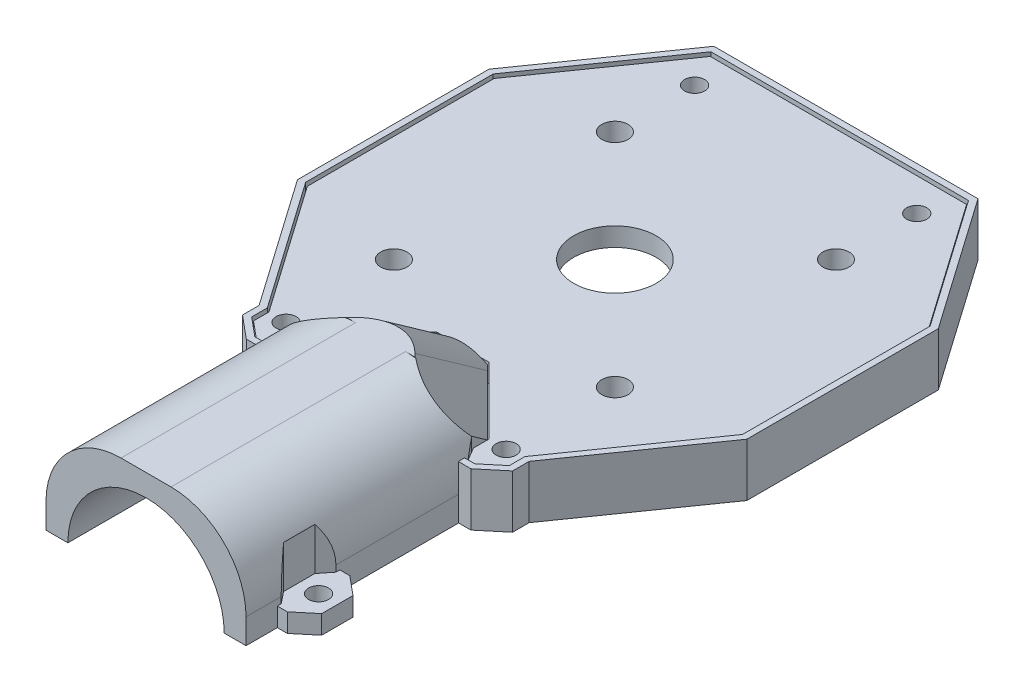
SolidWorks part; units mm, degrees
other "Base"
other "Plate"
material "ABS"
ref_plane "Front Plane" through (0, 0, 0) normal (0, 0, 1) x (1, 0, 0)
ref_plane "Top Plane" through (0, 0, 0) normal (0, 1, 0) x (1, 0, 0)
ref_plane "Right Plane" through (0, 0, 0) normal (1, 0, 0) x (0, 0, -1)
sketch "Sketch1" plane through (0, 0, 0) normal (0, 0, 1) x (1, 0, 0)
  line L0 (-16, 0) -> (16, 0)
  line L5 (-16, 0) -> (-16, 4)
  line L6 (-4, 16) -> (4, 16)
  line L7 (16, 4) -> (16, 0)
  circle A1 centre (0, 0) radius 12.5
  arc A2 (4, 16) -> (16, 4) centre (4, 4) cw
  arc A3 (-16, 4) -> (-4, 16) centre (-4, 4) cw
  point P4 (0, 0)
  point P9 (0, 0)
  point P15 (-16, 16)
  dimension "D1" = 25
  dimension "D4" = 12
  dimension "D2" = 32
  dimension "D3" = 16
extrude "Boss-Extrude1" add sketch "Sketch1" against normal blind 40 contours A3 L5 L0 A1 L7 A2 L6 region at (0, 12.8578, 0)
sketch "Sketch2" plane through (16, 0, 0) normal (1, 0, 0) x (0, 0, -1)
  line L0 (0, 0) -> (10, 0) construction
  line L1 (40, 0) -> (0, 0) construction
  point P5 (40, 0)
  dimension "D1" = 10
sketch "Sketch3" plane through (0, 0, 0) normal (0, 1, 0) x (1, 0, 0)
  line L0 (16, 10) -> (17.6, 10) construction
  line L1 (16, 0) -> (16, 10) construction
  line L2 (16, 40) -> (17.6, 40) construction
  line L3 (17.6, 5) -> (17.6, 15) construction
  line L4 (17.6, 10) -> (14.6, 10) construction
  line L5 (14.6, 7.5) -> (14.6, 12.5)
  line L10 (17.6, 10) -> (20.6, 10) construction
  line L11 (20.6, 7.5) -> (20.6, 12.5)
  line L12 (17.6, 15) -> (20.6, 12.5)
  line L13 (17.6, 5) -> (20.6, 7.5)
  line L14 (17.6, 5) -> (14.6, 5)
  line L15 (14.6, 5) -> (14.6, 7.5)
  line L16 (17.6, 15) -> (14.6, 15)
  line L17 (14.6, 15) -> (14.6, 12.5)
  line L18 (14.6, 7.5) -> (16, 6.3333)
  line L19 (14.6, 12.5) -> (16, 13.6667)
  line L20 (16, 13.6667) -> (16, 6.3333)
  line L21 (16, 6.3333) -> (17.5, 5.0833)
  line L22 (16, 13.6667) -> (17.5, 14.9167)
  circle A0 centre (17.6, 10) radius 1.6
  circle A1 centre (17.6, 40) radius 1.6
  point P14 (17.6, 10)
  point P18 (14.6, 10)
  point P19 (14.6, 10)
  point P25 (20.6, 10)
  dimension "D1" = 1.6
  dimension "D2" = 1.6
  dimension "D3" = 10
  dimension "D4" = 10
  dimension "D5" = 3
  dimension "D6" = 5
  dimension "D9" = 3
  dimension "D10" = 5
extrude "Boss-Extrude3" add sketch "Sketch3" along normal blind 3 contours L20 A0 L21 L14 L13 L11 L12 L16 L22 | L20 L19 L5 L18 | L21 L18 L15 L14 | L19 L22 L16 L17 region at (15.2253, 0, -6.8271) region at (15.3441, 0, -10)
sketch "Sketch5" plane through (0, 3, 0) normal (0, 1, 0) x (1, 0, 0)
  line L0 (16, 10) -> (14.5, 10) construction
  line L1 (14.5, 7.5) -> (14.5, 12.5)
  line L2 (14.5, 12.5) -> (16.5, 15)
  line L3 (16.5, 15) -> (16.5, 5)
  line L4 (16.5, 5) -> (14.5, 7.5)
  point P6 (14.5, 10)
  dimension "D1" = 1.5
  dimension "D2" = 5
  dimension "D3" = 10
  dimension "D4" = 2
extrude "Cut-Extrude5" cut sketch "Sketch5" along normal blind 17
sketch "Sketch6" plane through (0, 0, 0) normal (0, 1, 0) x (1, 0, 0)
  line L0 (16, 40) -> (17.6, 40) construction
  line L1 (17.6, 40) -> (14.6, 40) construction
  line L2 (16, 40) -> (4, 40) construction
  line L3 (14.6, 40) -> (14.6, 37.5)
  line L4 (17.6, 40) -> (17.6, 35) construction
  line L5 (-17.6, 40) -> (-20.6, 40) construction
  line L6 (14.6, 37.5) -> (14.6, 35)
  line L7 (14.6, 35) -> (17.6, 35)
  line L8 (17.6, 40) -> (20.6, 40) construction
  line L9 (20.6, 40) -> (20.6, 37.5)
  line L10 (17.6, 35) -> (20.6, 37.5)
  line L11 (-17.6, 40) -> (-17.6, 35) construction
  line L12 (-17.6, 40) -> (-14.6, 40) construction
  line L13 (-16, 40) -> (-17.6, 40) construction
  line L14 (0, 40) -> (0, 75) construction
  line L15 (-4, 40) -> (4, 40) construction
  line L16 (-17.6, 35) -> (-20.6, 37.5)
  line L17 (-20.6, 40) -> (-20.6, 37.5)
  line L18 (-14.6, 35) -> (-17.6, 35)
  line L19 (-14.6, 37.5) -> (-14.6, 35)
  line L20 (-14.6, 40) -> (-14.6, 37.5)
  line L21 (20.6, 40) -> (34.9394, 60.4788)
  line L22 (34.9394, 60.4788) -> (34.9394, 90.4788)
  line L23 (34.9394, 90.4788) -> (20.6, 110.9576)
  line L24 (20.6, 110.9576) -> (0.1, 110.9576)
  line L25 (29.9394, 62.0553) -> (18.4679, 45.6723)
  line L26 (-29.9394, 62.0553) -> (-18.4679, 45.6723)
  line L27 (-20.6, 40) -> (-34.9394, 60.4788)
  line L28 (-34.9394, 60.4788) -> (-34.9394, 90.4788)
  line L29 (-29.9394, 62.0553) -> (-29.9394, 88.9023)
  line L30 (-29.9394, 88.9023) -> (-17.9972, 105.9576)
  line L31 (29.9394, 62.0553) -> (29.9394, 88.9023)
  line L32 (29.9394, 88.9023) -> (17.9972, 105.9576)
  line L33 (17.9972, 105.9576) -> (0.1, 105.9576)
  line L34 (17.3978, 44.144) -> (17.3978, 44.144) construction
  line L35 (17.3978, 44.144) -> (29.9394, 62.0553) construction
  line L36 (17.3978, 44.144) -> (17.3978, 44.144) construction
  line L37 (17.3978, 44.144) -> (17.3978, 44.144) construction
  line L38 (17.3978, 44.144) -> (17.3978, 44.144) construction
  line L39 (17.3978, 44.144) -> (17.3978, 44.144) construction
  line L40 (-34.9394, 90.4788) -> (-20.6, 110.9576)
  line L41 (-17.9972, 105.9576) -> (0.1, 105.9576)
  line L42 (-20.6, 110.9576) -> (0.1, 110.9576)
  line L43 (0, 75) -> (-18.9667, 56.0333) construction
  line L44 (-14.6, 37.5) -> (-12.6, 37.5)
  line L45 (-12.6, 37.5) -> (-12.6, 45)
  line L46 (-12.6, 45) -> (-4.7764, 52.8236)
  line L47 (-4.7764, 52.8236) -> (4.7764, 52.8236)
  line L48 (14.6, 37.5) -> (12.6, 37.5)
  line L49 (12.6, 37.5) -> (12.6, 45)
  line L50 (12.6, 45) -> (4.7764, 52.8236)
  line L51 (-12.6, 37.5) -> (12.6, 37.5)
  line L52 (-17.9972, 105.9576) -> (-17.7663, 105.5141) construction
  line L53 (-29.9394, 75.4788) -> (-29.9394, 78.4788) construction
  line L54 (-29.9394, 75.4788) -> (-29.9394, 72.4788) construction
  line L55 (29.9394, 75.4788) -> (29.9394, 78.4788) construction
  line L56 (29.9394, 75.4788) -> (29.9394, 72.4788) construction
  circle A0 centre (17.6, 40) radius 1.6
  circle A1 centre (0, 75) radius 6.6
  circle A2 centre (0, 75) radius 12.5 construction
  circle A3 centre (0, 75) radius 25 construction
  circle A16 centre (-17.6, 40) radius 1.6
  circle A17 centre (-17.6777, 57.3223) radius 2.1
  arc A18 (-18.4679, 45.6723) -> (-12.6, 45) centre (-15.1475, 48.7095) ccw
  arc A19 (18.4679, 45.6723) -> (12.6, 45) centre (15.1475, 48.7095) cw
  circle A20 centre (-17.6777, 92.6777) radius 2.1
  circle A21 centre (17.6777, 92.6777) radius 2.1
  circle A22 centre (17.6777, 57.3223) radius 2.1
  circle A24 centre (-17.7663, 105.5141) radius 1.6
  arc A25 (-19.9473, 103.1725) -> (-14.5972, 105.9576) centre (-17.7663, 105.5141) ccw
  circle A28 centre (17.7663, 105.5141) radius 1.6
  arc A29 (19.9473, 103.1725) -> (14.5972, 105.9576) centre (17.7663, 105.5141) cw
  point P59 (0, 52.8236)
  point P72 (0, 75)
  dimension "D6" = 13.2
  dimension "D7" = 25
  dimension "D8" = 50
  dimension "D9" = 145
  dimension "D11" = 45
  dimension "D19" = 4.2
  dimension "D24" = 4.5
  dimension "D27" = 3.2
  dimension "D28" = 3.2
  dimension "D1" = 1.6
  dimension "D2" = 3
  dimension "D3" = 2.5
  dimension "D4" = 5
  dimension "D5" = 3
  dimension "D13" = 35
  dimension "D10" = 25
  dimension "D12" = 145
  dimension "D14" = 30
  dimension "D15" = 20.5
  dimension "D17" = 145
  dimension "D18" = 20
  dimension "D20" = 2
  dimension "D21" = 7.5
  dimension "D22" = 135
  dimension "D23" = 4.7764
  dimension "D26" = 0.5
  dimension "D30" = 3
  dimension "D31" = 3
  dimension "D34" = 3
  dimension "D35" = 3
  dimension "D16" = 5
  dimension "D25" = 4
extrude "Boss-Extrude4" add sketch "Sketch6" along normal blind 5 contours L33 A28 L32 L31 L25 A19 L49 L48 L6 L7 L10 L9 L21 L22 L23 L24 L42 L40 L28 L27 L17 L16 L18 L19 L44 L45 A18 L26 L29 L30 A24 L41 A16 A0 | L30 A25 L41 A24 | A29 L32 A28 L33 | L45 L51 L49 L50 L47 L46 region at (13.6, 0, -38.5321) region at (0, 0, -44.2098) region at (16.9071, 0, -103.8637) region at (-16.9071, 0, -103.8637)
sketch "Sketch7" plane through (0, 5, 0) normal (0, 1, 0) x (1, 0, 0)
  line L7 (0, 40) -> (0, 40.7314) construction
  line L13 (-16.1, 35) -> (-14.6, 37.5)
  line L14 (-14.6, 35) -> (-17.6, 35) construction
  line L15 (-14.6, 37.5) -> (-14.6, 40)
  line L16 (-14.6, 40) -> (-16.1, 40)
  line L17 (-17.6, 40) -> (-14.6, 40) construction
  line L18 (-16.1, 40) -> (-16.1, 35)
  line L19 (16.1, 40) -> (16.1, 35)
  line L20 (14.6, 40) -> (16.1, 40)
  line L21 (14.6, 37.5) -> (14.6, 40)
  line L22 (16.1, 35) -> (14.6, 37.5)
extrude "Cut-Extrude7" cut sketch "Sketch7" along normal blind 40
sketch "Sketch8" plane through (0, 5, 0) normal (0, 1, 0) x (1, 0, 0)
  line L0 (-14.6, 40) -> (-4.1, 50.5)
  line L1 (-4.1, 50.5) -> (4.1, 50.5)
  line L2 (4.1, 50.5) -> (14.6, 40)
  line L3 (-14.6, 40) -> (-14.6, 37.5)
  line L4 (-14.6, 37.5) -> (14.6, 37.5)
  line L5 (14.6, 37.5) -> (14.6, 40)
  dimension "D1" = 135
  dimension "D2" = 135
  dimension "D3" = 13
extrude "Boss-Extrude5" add sketch "Sketch8" along normal up to surface (11 mm away) up to face at (0, 16, -20)
sketch "Sketch9" plane through (0, 0, -37.5) normal (0, 0, 1) x (1, 0, 0)
  line L1 (-12.5, 0) -> (12.5, 0)
  line L2 (-12.5, 0) -> (12.5, 0)
  arc A1 (12.5, 0) -> (-12.5, 0) centre (0, 0) ccw
  arc A2 (12.5, 0) -> (-12.5, 0) centre (0, 0) ccw
  dimension "D1" = 0
extrude "Cut-Extrude8" cut sketch "Sketch9" against normal blind 3
mirror "Mirror1" about plane through (0, 0, 0) normal (1, 0, 0) of "Boss-Extrude3"
mirror "Mirror2" about plane through (0, 0, 0) normal (1, 0, 0) of "Cut-Extrude5"
sketch "Sketch10" plane through (0, 5, 0) normal (0, 1, 0) x (1, 0, 0)
  line L0 (20.6, 110.9576) -> (-20.6, 110.9576) construction
  line L1 (34.9394, 90.4788) -> (20.6, 110.9576) construction
  line L2 (34.9394, 60.4788) -> (34.9394, 90.4788) construction
  line L3 (20.6, 40) -> (34.9394, 60.4788) construction
  line L4 (20.6, 40) -> (20.6, 37.5) construction
  line L5 (17.6, 35) -> (20.6, 37.5) construction
  line L6 (15.9583, 35) -> (17.6, 35) construction
  line L7 (-15.9583, 35) -> (-17.6, 35) construction
  line L8 (-17.6, 35) -> (-20.6, 37.5) construction
  line L9 (-20.6, 40) -> (-20.6, 37.5) construction
  line L10 (-20.6, 40) -> (-34.9394, 60.4788) construction
  line L11 (-34.9394, 60.4788) -> (-34.9394, 90.4788) construction
  line L12 (-34.9394, 90.4788) -> (-20.6, 110.9576) construction
  line L13 (20.6, 110.9576) -> (-20.6, 110.9576)
  line L14 (34.9394, 90.4788) -> (20.6, 110.9576)
  line L15 (34.9394, 60.4788) -> (34.9394, 90.4788)
  line L16 (20.6, 40) -> (34.9394, 60.4788)
  line L17 (20.6, 40) -> (20.6, 37.5)
  line L18 (17.6, 35) -> (20.6, 37.5)
  line L19 (15.9583, 35) -> (17.6, 35)
  line L20 (-15.9583, 35) -> (-17.6, 35)
  line L21 (-17.6, 35) -> (-20.6, 37.5)
  line L22 (-20.6, 40) -> (-20.6, 37.5)
  line L23 (-20.6, 40) -> (-34.9394, 60.4788)
  line L24 (-34.9394, 60.4788) -> (-34.9394, 90.4788)
  line L25 (-34.9394, 90.4788) -> (-20.6, 110.9576)
  line L26 (15.9583, 34) -> (17.962, 34)
  line L27 (17.962, 34) -> (21.6, 37.0316)
  line L28 (21.6, 39.6847) -> (21.6, 37.0316)
  line L29 (21.6, 39.6847) -> (35.9394, 60.1635)
  line L30 (35.9394, 60.1635) -> (35.9394, 90.7941)
  line L31 (35.9394, 90.7941) -> (21.1206, 111.9576)
  line L32 (21.1206, 111.9576) -> (-21.1206, 111.9576)
  line L33 (-35.9394, 90.7941) -> (-21.1206, 111.9576)
  line L34 (-35.9394, 60.1635) -> (-35.9394, 90.7941)
  line L35 (-21.6, 39.6847) -> (-35.9394, 60.1635)
  line L36 (-21.6, 39.6847) -> (-21.6, 37.0316)
  line L37 (-17.962, 34) -> (-21.6, 37.0316)
  line L38 (-15.9583, 34) -> (-17.962, 34)
  line L39 (-15.9583, 34) -> (-15.9583, 35)
  line L40 (15.9583, 34) -> (15.9583, 35)
  dimension "D1" = 1
extrude "Boss-Extrude7" add sketch "Sketch10" along normal blind 3.5 and the other way blind 5
sketch "Sketch13" plane through (0, 5, 0) normal (0, 1, 0) x (1, 0, 0)
  line L0 (-20.4959, 110.7576) -> (-34.7394, 90.4157)
  line L1 (-34.7394, 90.4157) -> (-34.7394, 60.5419)
  line L2 (-34.7394, 60.5419) -> (-20.4, 40.0631)
  line L3 (-20.4, 40.0631) -> (-20.4, 37.5937)
  line L4 (-20.4, 37.5937) -> (-17.5276, 35.2)
  line L5 (-17.5276, 35.2) -> (-16.1583, 35.2)
  line L6 (-16.1583, 35.2) -> (-16.1583, 35.2916)
  line L7 (-16.1583, 35.2916) -> (-14.8, 37.5554)
  line L8 (-14.8, 37.5554) -> (-14.8, 40.0828)
  line L9 (-14.8, 40.0828) -> (-4.1828, 50.7)
  line L10 (-4.1828, 50.7) -> (4.1828, 50.7)
  line L11 (4.1828, 50.7) -> (14.8, 40.0828)
  line L12 (14.8, 40.0828) -> (14.8, 37.5554)
  line L13 (14.8, 37.5554) -> (16.1583, 35.2916)
  line L14 (16.1583, 35.2916) -> (16.1583, 35.2)
  line L15 (16.1583, 35.2) -> (17.5276, 35.2)
  line L16 (17.5276, 35.2) -> (20.4, 37.5937)
  line L17 (20.4, 37.5937) -> (20.4, 40.0631)
  line L18 (20.4, 40.0631) -> (34.7394, 60.5419)
  line L19 (34.7394, 60.5419) -> (34.7394, 90.4157)
  line L20 (34.7394, 90.4157) -> (20.4959, 110.7576)
  line L21 (20.4959, 110.7576) -> (-20.4959, 110.7576)
  line L22 (-14.6, 37.5) -> (-14.6, 40)
  line L23 (-14.6, 40) -> (-4.1, 50.5)
  line L24 (-4.1, 50.5) -> (4.1, 50.5)
  line L25 (4.1, 50.5) -> (14.6, 40)
  line L26 (14.6, 40) -> (14.6, 37.5)
  line L27 (14.6, 37.5) -> (15.9583, 35.2362)
  line L28 (15.9583, 35.2362) -> (15.9583, 35)
  line L29 (15.9583, 35) -> (17.6, 35)
  line L30 (17.6, 35) -> (20.6, 37.5)
  line L31 (20.6, 37.5) -> (20.6, 40)
  line L32 (20.6, 40) -> (34.9394, 60.4788)
  line L33 (34.9394, 60.4788) -> (34.9394, 90.4788)
  line L34 (34.9394, 90.4788) -> (20.6, 110.9576)
  line L35 (20.6, 110.9576) -> (-20.6, 110.9576)
  line L36 (-20.6, 110.9576) -> (-34.9394, 90.4788)
  line L37 (-34.9394, 90.4788) -> (-34.9394, 60.4788)
  line L38 (-34.9394, 60.4788) -> (-20.6, 40)
  line L39 (-20.6, 40) -> (-20.6, 37.5)
  line L40 (-20.6, 37.5) -> (-17.6, 35)
  line L41 (-17.6, 35) -> (-15.9583, 35)
  line L42 (-15.9583, 35) -> (-15.9583, 35.2362)
  line L43 (-15.9583, 35.2362) -> (-14.6, 37.5)
  line L44 (-14.6, 37.5) -> (-14.6, 40)
  line L45 (-14.6, 40) -> (-4.1, 50.5)
  line L46 (-4.1, 50.5) -> (4.1, 50.5)
  line L47 (4.1, 50.5) -> (14.6, 40)
  line L48 (14.6, 40) -> (14.6, 37.5)
  line L49 (14.6, 37.5) -> (15.9583, 35.2362)
  line L50 (15.9583, 35.2362) -> (15.9583, 35)
  line L51 (15.9583, 35) -> (17.6, 35)
  line L52 (17.6, 35) -> (20.6, 37.5)
  line L53 (20.6, 37.5) -> (20.6, 40)
  line L54 (20.6, 40) -> (34.9394, 60.4788)
  line L55 (34.9394, 60.4788) -> (34.9394, 90.4788)
  line L56 (34.9394, 90.4788) -> (20.6, 110.9576)
  line L57 (20.6, 110.9576) -> (-20.6, 110.9576)
  line L58 (-20.6, 110.9576) -> (-34.9394, 90.4788)
  line L59 (-34.9394, 90.4788) -> (-34.9394, 60.4788)
  line L60 (-34.9394, 60.4788) -> (-20.6, 40)
  line L61 (-20.6, 40) -> (-20.6, 37.5)
  line L62 (-20.6, 37.5) -> (-17.6, 35)
  line L63 (-17.6, 35) -> (-15.9583, 35)
  line L64 (-15.9583, 35) -> (-15.9583, 35.2362)
  line L65 (-15.9583, 35.2362) -> (-14.6, 37.5)
  circle A0 centre (17.6, 40) radius 1.6 construction
  circle A1 centre (-17.6, 40) radius 1.6 construction
  circle A2 centre (-17.6777, 57.3223) radius 2.1 construction
  circle A3 centre (17.6777, 57.3223) radius 2.1 construction
  circle A4 centre (17.6777, 92.6777) radius 2.1 construction
  circle A5 centre (17.7663, 105.5141) radius 1.6 construction
  circle A6 centre (-17.7663, 105.5141) radius 1.6 construction
  circle A7 centre (-17.6777, 92.6777) radius 2.1 construction
  circle A8 centre (17.6, 40) radius 1.6
  circle A9 centre (-17.6, 40) radius 1.6
  circle A10 centre (-17.6777, 57.3223) radius 2.1
  circle A11 centre (17.6777, 57.3223) radius 2.1
  circle A12 centre (17.6777, 92.6777) radius 2.1
  circle A13 centre (17.7663, 105.5141) radius 1.6
  circle A14 centre (-17.7663, 105.5141) radius 1.6
  circle A15 centre (-17.6777, 92.6777) radius 2.1
  circle A16 centre (0, 75) radius 6.6 construction
  circle A17 centre (0, 75) radius 6.6
  circle M23 centre (-17.6, 40) radius 1.6
  circle M24 centre (17.6, 40) radius 1.6
  line M25 (-14.5972, 105.9576) -> (14.5972, 105.9576)
  arc M26 (14.5972, 105.9576) -> (19.9473, 103.1725) centre (17.7663, 105.5141) ccw
  line M27 (19.9473, 103.1725) -> (29.9394, 88.9023)
  line M28 (29.9394, 88.9023) -> (29.9394, 62.0553)
  line M29 (29.9394, 62.0553) -> (18.4679, 45.6723)
  arc M30 (18.4679, 45.6723) -> (12.6, 45) centre (15.1475, 48.7095) cw
  line M31 (12.6, 45) -> (4.7764, 52.8236)
  line M32 (4.7764, 52.8236) -> (-4.7764, 52.8236)
  line M33 (-4.7764, 52.8236) -> (-12.6, 45)
  arc M34 (-12.6, 45) -> (-18.4679, 45.6723) centre (-15.1475, 48.7095) cw
  line M35 (-18.4679, 45.6723) -> (-29.9394, 62.0553)
  line M36 (-29.9394, 62.0553) -> (-29.9394, 88.9023)
  line M37 (-29.9394, 88.9023) -> (-19.9473, 103.1725)
  arc M38 (-19.9473, 103.1725) -> (-14.5972, 105.9576) centre (-17.7663, 105.5141) ccw
  circle M39 centre (-17.7663, 105.5141) radius 1.6
  circle M40 centre (17.7663, 105.5141) radius 1.6
  dimension "D1" = 0
  dimension "D2" = 0.2
extrude "Boss-Extrude8" add sketch "Sketch13" along normal blind 3 separate body contours L20 L21 L0 L1 L2 L3 L4 L5 L7 L8 L9 L10 L11 L12 L13 L15 L16 L17 L18 L19 M23 M38 M25 M26 M27 M28 M29 M30 M31 M32 M33 M34 M35 M36 M37 M39 M40 M24 | A15 A12 A11 A10 M25 M38 M37 M36 M35 M34 M33 M32 M31 M30 M29 M28 M27 M26 region at (0, 5, -109.7311) region at (0, 5, -105.0975)
chamfer "Chamfer1" distance 8.2 angle 45 2 edges at (-9.35, 16, -45.25) (9.35, 16, -45.25)
fillet "Fillet1" radius 10 1 edges at (0, 13.3496, -46.7517)
sketch "Sketch14" plane through (0, 0, -40.5) normal (0, 0, 1) x (1, 0, 0)
  line L0 (-11, 0) -> (11, 0)
  circle A0 centre (0, 0) radius 11
  line M2 (-12.5, 0) -> (12.5, 0)
  dimension "D1" = 22
extrude "Boss-Extrude9" add sketch "Sketch14" along normal blind 10 contours A0 M2 region at (0, 4.6685, -40.5)
